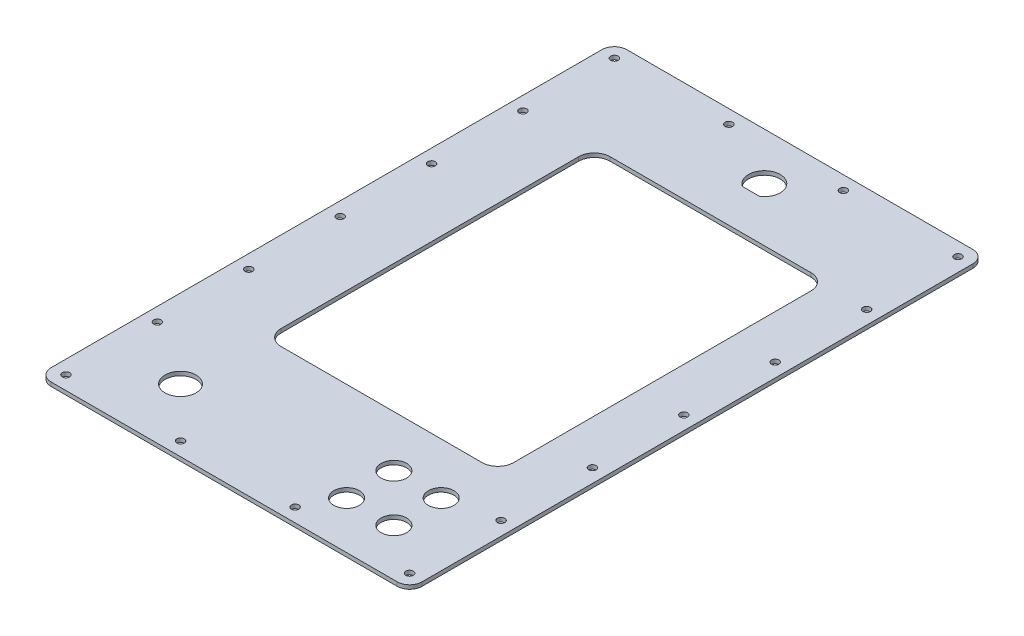
SolidWorks part; units mm, degrees
material "5052-H32"
ref_plane "Front Plane" through (0, 0, 0) normal (0, 0, 1) x (1, 0, 0)
ref_plane "Top Plane" through (0, 0, 0) normal (0, 1, 0) x (1, 0, 0)
ref_plane "Right Plane" through (0, 0, 0) normal (1, 0, 0) x (0, 0, -1)
sketch "Sketch9" plane through (0, 0, 0) normal (0, 1, 0) x (1, 0, 0)
  line L0 (-149.5, 0) -> (-149.5, 464)
  line L13 (-149.5, 464) -> (149.5, 464)
  line L14 (103.1625, 117.4438) -> (-84.1625, 117.4438)
  line L19 (149.5, 464) -> (149.5, 0)
  line L20 (103.1625, 117.4438) -> (103.1625, 382.5563)
  line L21 (103.1625, 382.5563) -> (-84.1625, 382.5563)
  line L22 (-84.1625, 117.4438) -> (-84.1625, 382.5563)
  line L23 (103.1625, 250) -> (-84.1625, 250) construction
  line L24 (9.5, 382.5562) -> (9.5, 117.4438) construction
  line L25 (-149.5, 0) -> (149.5, 0)
  line L26 (9.5, 464) -> (9.5, 425.9) construction
  line L27 (16.3702, 415.1) -> (2.6298, 415.1)
  arc A0 (16.3702, 415.1) -> (2.6298, 415.1) centre (9.5, 425.9) ccw
  circle A1 centre (-86, 50.8) radius 12.5
  circle A2 centre (98.7, 76.2) radius 10.287
  circle A3 centre (98.7, 38.1) radius 10.287
  circle A4 centre (60.6, 76.2) radius 10.287
  circle A5 centre (60.6, 38.1) radius 10.287
  point P8 (0, 0)
  point P17 (9.5, 438.7)
  point P19 (0, 0)
  point P30 (-75.7397, 80.6094)
  point P31 (-98.7, 80.6094)
  point P32 (-80.1653, 51.7957)
  point P33 (-98.7, 76.2)
  point P34 (0, 0)
  point P35 (60.6, 58.6005)
  point P36 (0, 0)
  point P37 (0, 0)
  point P38 (0, 0)
  point P39 (60.6, 38.1)
  point P40 (0, 0)
  point P41 (0, 0)
  dimension "D8" = 25.6
  dimension "D10" = 25
  dimension "D11" = 20.574
  dimension "D3" = 265.1125
  dimension "D4" = 187.325
  dimension "D1" = 299
  dimension "D2" = 464
  dimension "D6" = 140
  dimension "D5" = 214
  dimension "D7" = 23.6
  dimension "D9" = 38.1
  dimension "D12" = 38.1
  dimension "D13" = 38.1
  dimension "D15" = 38.1
  dimension "D16" = 50.8
  dimension "D17" = 63.5
  dimension "D14" = 50.8
extrude "Boss-Extrude7" add sketch "Sketch9" along normal blind 3.175 separate body contours L0 L25 L19 L13 L14 L22 L21 L20 region at (-143.9801, 0, -232)
fillet "Fillet4" radius 10 4 edges at (-149.5, 1.5875, -464) (149.5, 1.5875, -464) (-149.5, 1.5875, 0) (149.5, 1.5875, 0)
fillet "Fillet5" radius 12.7 4 edges at (-84.1625, 1.5875, -117.4438) (103.1625, 1.5875, -117.4438) (103.1625, 1.5875, -382.5563) (-84.1625, 1.5875, -382.5563)
sketch "Sketch10" plane through (0, 3.175, 0) normal (0, 1, 0) x (1, 0, 0)
  line L0 (-149.5, 10) -> (-149.5, 454) construction
  line L1 (-139.5, 0) -> (139.5, 0) construction
  circle A0 centre (-138.5, 11) radius 3
  circle A1 centre (-46.1667, 11) radius 3
  circle A2 centre (46.1667, 11) radius 3
  circle A3 centre (138.5, 11) radius 3
  circle A56 centre (-138.5, 84.6667) radius 3
  circle A57 centre (-138.5, 158.3333) radius 3
  circle A58 centre (-138.5, 232) radius 3
  circle A59 centre (-138.5, 305.6667) radius 3
  circle A60 centre (-138.5, 379.3333) radius 3
  circle A61 centre (-138.5, 453) radius 3
  circle A68 centre (138.5, 84.6667) radius 3
  circle A72 centre (138.5, 158.3333) radius 3
  circle A76 centre (138.5, 232) radius 3
  circle A80 centre (138.5, 305.6667) radius 3
  circle A84 centre (138.5, 379.3333) radius 3
  circle A86 centre (-46.1667, 453) radius 3
  circle A87 centre (46.1667, 453) radius 3
  circle A88 centre (138.5, 453) radius 3
  circle A102 centre (-46.1667, 84.6667) radius 3 [skipped]
  circle A103 centre (46.1667, 84.6667) radius 3 [skipped]
  circle A104 centre (-46.1667, 158.3333) radius 3 [skipped]
  circle A105 centre (46.1667, 158.3333) radius 3 [skipped]
  circle A106 centre (-46.1667, 232) radius 3 [skipped]
  circle A107 centre (46.1667, 232) radius 3 [skipped]
  circle A108 centre (-46.1667, 305.6667) radius 3 [skipped]
  circle A109 centre (46.1667, 305.6667) radius 3 [skipped]
  circle A110 centre (-46.1667, 379.3333) radius 3 [skipped]
  circle A111 centre (46.1667, 379.3333) radius 3 [skipped]
  dimension "D1" = 6
  dimension "D2" = 11
  dimension "D3" = 11
  dimension "D6" = 73.6667
  dimension "D7" = 92.3333
  dimension "D4" = 4
  dimension "D5" = 7
extrude "Cut-Extrude1" cut sketch "Sketch10" against normal up to surface (3.175 mm away) up to face at (60.6, 0, -27.813)
equation "\"W\"= 255mm"
equation "\"L\"= 420mm"
equation "\"Offset\"= 16mm"
equation "\"H\"= 110mm"
equation "\"T\"= 4.7625 * 2 / 3mm"
equation "\"Inside Fillet Radius\"= 5.55625mm"
equation "\"Hole\"=25mm"
equation "\"D1@Sketch9\"=\"W\"+44"
equation "\"D2@Sketch9\"=\"L\"+44"
equation "\"D6@Sketch10\"=(\"L\"+22)/6"
equation "\"D7@Sketch10\"=(\"W\"+22)/3"
equation "\"D5@Sketch9\"=(\"L\"/2+20)-\"Offset\""
equation "\"Compartment Width1\"= 90mm"
equation "\"Compartment Width2\"= 90mm"
